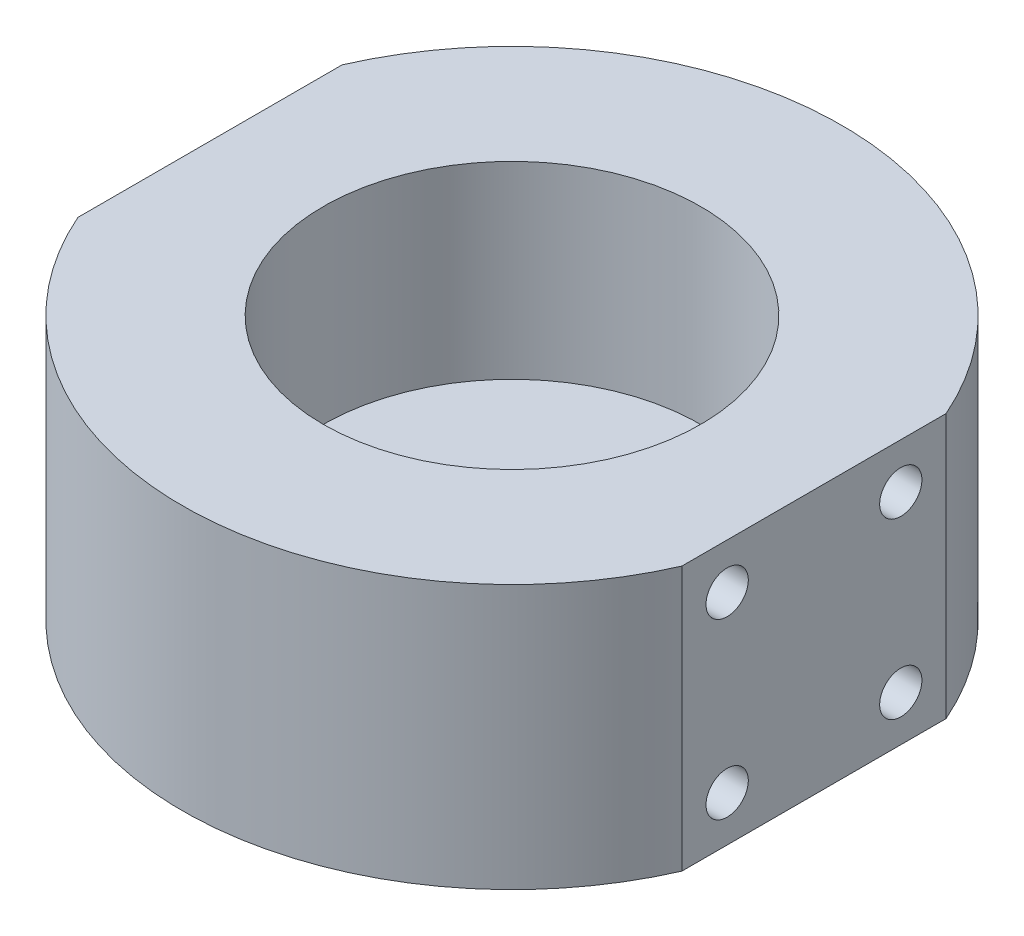
SolidWorks part; units mm, degrees
ref_plane "Front Plane" through (0, 0, 0) normal (0, 0, 1) x (1, 0, 0)
ref_plane "Top Plane" through (0, 0, 0) normal (0, 1, 0) x (1, 0, 0)
ref_plane "Right Plane" through (0, 0, 0) normal (1, 0, 0) x (0, 0, -1)
sketch "Sketch1" plane through (0, 0, 0) normal (0, 1, 0) x (1, 0, 0)
  line L0 (-40, 17.5) -> (-40, -17.5)
  line L1 (40, 17.5) -> (40, -17.5)
  arc A0 (-40, -17.5) -> (40, -17.5) centre (0, 0) ccw
  arc A1 (40, 17.5) -> (-40, 17.5) centre (0, 0) ccw
  point P7 (-40, 0)
  point P8 (-40, 18.0377)
  dimension "D1" = 40
  dimension "D2" = 35
extrude "Boss-Extrude1" add sketch "Sketch1" along normal blind 35
sketch "Sketch2" plane through (-40, 0, 0) normal (-1, 0, 0) x (0, 0, 1)
  line L0 (0, 0) -> (0, 35) construction
  line L1 (-17.5, 35) -> (17.5, 35) construction
  line L2 (-17.5, 17.5) -> (17.5, 17.5) construction
  line L3 (-17.5, 35) -> (-17.5, 0) construction
  line L4 (17.5, 35) -> (17.5, 0) construction
  circle A0 centre (-11.5, 29) radius 2.8
  circle A1 centre (11.5, 29) radius 2.8
  circle A2 centre (-11.5, 6) radius 2.8
  circle A3 centre (11.5, 6) radius 2.8
  dimension "D1" = 5.6
  dimension "D2" = 23
  dimension "D3" = 23
extrude "Cut-Extrude1" cut sketch "Sketch2" against normal blind 10
extrude "Cut-Extrude2" cut sketch "Sketch2<2>" along normal blind 10 from surface starting at face at (40, 17.5, 0)
sketch "Sketch2<2>" plane through (-40, 0, 0) normal (-1, 0, 0) x (0, 0, 1) same geometry as "Sketch2"
sketch "Sketch3" plane through (0, 35, 0) normal (0, 1, 0) x (1, 0, 0)
  line L0 (0, -9) -> (0, 9) construction
  line L1 (-6, 0) -> (6, 0) construction
  circle A0 centre (0, 9) radius 1.69
  circle A1 centre (6, 0) radius 1.69
  circle A2 centre (0, -9) radius 1.69
  circle A3 centre (-6, 0) radius 1.69
  circle A4 centre (0, 0) radius 2.25
  point P5 (0, 0)
  point P6 (0, 0)
  dimension "D3" = 4.5
  dimension "D4" = 3.38
  dimension "D1" = 18
  dimension "D2" = 12
extrude "Cut-Extrude3" cut sketch "Sketch3" against normal through all
sketch "Sketch4" plane through (0, 35, 0) normal (0, 1, 0) x (1, 0, 0)
  circle A4 centre (0, 0) radius 25
  dimension "D2" = 50
extrude "Cut-Extrude4" cut sketch "Sketch4" against normal offset from surface (25 mm away) 10 up to face at (6, 0, 1.69)
